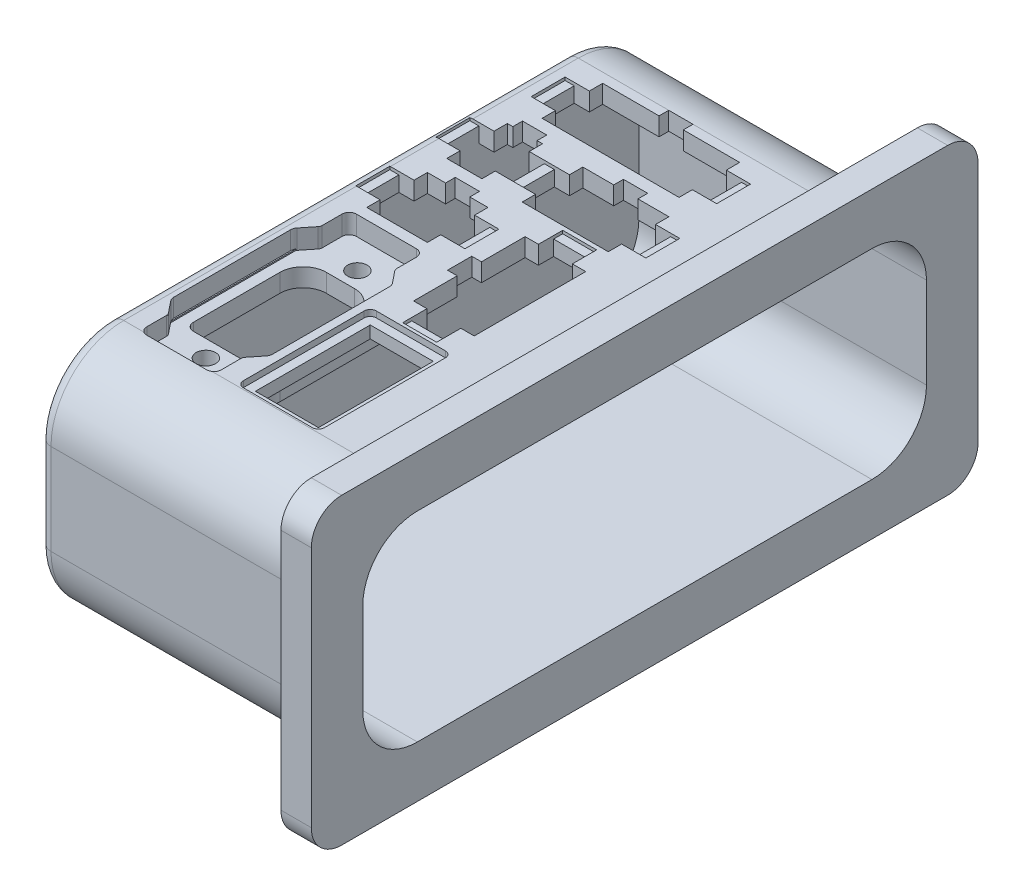
SolidWorks part; units mm, degrees
note: The reader was unsure of these and kept them because the rebuilt part matched: shared geometry of "Sketch1<3>".
ref_plane "Front Plane" through (0, 0, 0) normal (0, 0, 1) x (1, 0, 0)
ref_plane "Top Plane" through (0, 0, 0) normal (0, 1, 0) x (1, 0, 0)
ref_plane "Right Plane" through (0, 0, 0) normal (1, 0, 0) x (0, 0, -1)
sketch "Sketch1" plane through (-330.42, 0, 0) normal (-1, 0, 0) x (0, 0, 1)
  line L47 (-96.595, 23.5) -> (-96.595, 62.5)
  line L48 (-195.595, 23.5) -> (-96.595, 23.5)
  line L49 (-195.595, 62.5) -> (-195.595, 23.5)
  line L50 (-96.595, 62.5) -> (-195.595, 62.5)
  line L51 (-96.595, 35.5) -> (-96.595, 50.5)
  line L52 (-183.595, 23.5) -> (-108.595, 23.5)
  line L53 (-195.595, 50.5) -> (-195.595, 35.5)
  line L54 (-108.595, 62.5) -> (-183.595, 62.5)
  arc A12 (-96.595, 50.5) -> (-108.595, 62.5) centre (-108.595, 50.5) ccw
  arc A13 (-96.595, 35.5) -> (-108.595, 23.5) centre (-108.595, 35.5) cw
  arc A14 (-195.595, 35.5) -> (-183.595, 23.5) centre (-183.595, 35.5) ccw
  arc A15 (-195.595, 50.5) -> (-183.595, 62.5) centre (-183.595, 50.5) cw
  dimension "D1" = 0.5
  dimension "D2" = 12
extrude "Boss-Extrude1" add sketch "Sketch1" against normal blind 10.45
sketch "Sketch2" plane through (-319.97, 0, 0) normal (1, 0, 0) x (0, 0, -1)
  line L10 (51.095, 23) -> (51.095, 63)
  line L11 (46.095, 68) -> (-53.905, 68)
  line L12 (-58.905, 63) -> (-58.905, 23)
  line L13 (-53.905, 18) -> (46.095, 18)
  line L14 (201.095, 18) -> (201.095, 68)
  line L15 (91.095, 18) -> (201.095, 18)
  line L16 (91.095, 68) -> (91.095, 18)
  line L17 (201.095, 68) -> (91.095, 68)
  line L18 (201.095, 23) -> (201.095, 63)
  line L19 (96.095, 18) -> (196.095, 18)
  line L20 (91.095, 63) -> (91.095, 23)
  line L21 (196.095, 68) -> (96.095, 68)
  line L22 (-98.905, 23) -> (-98.905, 63)
  line L23 (-103.905, 68) -> (-203.905, 68)
  line L24 (-208.905, 63) -> (-208.905, 23)
  line L25 (-203.905, 18) -> (-103.905, 18)
  line L27 (-53.905, 63) -> (46.095, 63) construction
  arc A0 (201.095, 63) -> (196.095, 68) centre (196.095, 63) ccw
  arc A1 (201.095, 23) -> (196.095, 18) centre (196.095, 23) cw
  arc A2 (96.095, 18) -> (91.095, 23) centre (96.095, 23) cw
  arc A3 (91.095, 63) -> (96.095, 68) centre (96.095, 63) cw
  arc A4 (51.095, 23) -> (46.095, 18) centre (46.095, 23) cw
  arc A5 (51.095, 63) -> (46.095, 68) centre (46.095, 63) ccw
  arc A6 (-58.905, 63) -> (-53.905, 68) centre (-53.905, 63) cw
  arc A7 (-53.905, 18) -> (-58.905, 23) centre (-53.905, 23) cw
  arc A8 (-98.905, 23) -> (-103.905, 18) centre (-103.905, 23) cw
  arc A9 (-98.905, 63) -> (-103.905, 68) centre (-103.905, 63) ccw
  arc A10 (-208.905, 63) -> (-203.905, 68) centre (-203.905, 63) cw
  arc A11 (-203.905, 18) -> (-208.905, 23) centre (-203.905, 23) cw
  point P44 (-3.905, 63)
  point P45 (-3.905, 68)
  dimension "D2" = 5
  dimension "D1" = 5
  dimension "D3" = 3
extrude "Boss-Extrude2" add sketch "Sketch2" along normal blind 5
delete or keep bodies "Body-Delete/Keep 1" type delete bodies bodies 115
delete or keep bodies "Body-Delete/Keep 2" type delete bodies bodies 114
sketch "Sketch8" plane through (-330.42, 0, 0) normal (-1, 0, 0) x (0, 0, 1)
  line L0 (-108.595, 59.5) -> (-183.595, 59.5)
  line L1 (-192.595, 50.5) -> (-192.595, 35.5)
  line L2 (-183.595, 26.5) -> (-108.595, 26.5)
  line L3 (-99.595, 35.5) -> (-99.595, 50.5)
  line L4 (-108.595, 62.5) -> (-183.595, 62.5)
  line L5 (-195.595, 50.5) -> (-195.595, 35.5)
  line L6 (-183.595, 23.5) -> (-108.595, 23.5)
  line L7 (-96.595, 35.5) -> (-96.595, 50.5)
  line L8 (-108.595, 62.5) -> (-183.595, 62.5)
  line L9 (-195.595, 50.5) -> (-195.595, 35.5)
  line L10 (-183.595, 23.5) -> (-108.595, 23.5)
  line L11 (-96.595, 35.5) -> (-96.595, 50.5)
  line L12 (-195.595, 50.5) -> (-195.595, 62.5)
  line L13 (-195.595, 62.5) -> (-183.595, 62.5)
  line L14 (-183.595, 59.5) -> (-190.595, 59.5)
  line L15 (-192.595, 57.5) -> (-192.595, 50.5)
  line L16 (-108.595, 59.5) -> (-101.595, 59.5)
  line L17 (-99.595, 57.5) -> (-99.595, 50.5)
  line L18 (-96.595, 50.5) -> (-96.595, 62.5)
  line L19 (-96.595, 62.5) -> (-108.595, 62.5)
  arc A2 (-192.595, 35.5) -> (-183.595, 26.5) centre (-183.595, 35.5) ccw
  arc A3 (-108.595, 26.5) -> (-99.595, 35.5) centre (-108.595, 35.5) ccw
  arc A4 (-96.595, 50.5) -> (-108.595, 62.5) centre (-108.595, 50.5) ccw
  arc A5 (-183.595, 62.5) -> (-195.595, 50.5) centre (-183.595, 50.5) ccw
  arc A6 (-195.595, 35.5) -> (-183.595, 23.5) centre (-183.595, 35.5) ccw
  arc A7 (-108.595, 23.5) -> (-96.595, 35.5) centre (-108.595, 35.5) ccw
  arc A10 (-195.595, 35.5) -> (-183.595, 23.5) centre (-183.595, 35.5) ccw
  arc A11 (-108.595, 23.5) -> (-96.595, 35.5) centre (-108.595, 35.5) ccw
  arc A12 (-101.595, 59.5) -> (-99.595, 57.5) centre (-101.595, 57.5) cw
  arc A13 (-190.595, 59.5) -> (-192.595, 57.5) centre (-190.595, 57.5) ccw
  arc A16 (-183.595, 62.5) -> (-195.595, 50.5) centre (-183.595, 50.5) ccw construction
  arc A17 (-183.595, 59.5) -> (-192.595, 50.5) centre (-183.595, 50.5) ccw construction
  arc A18 (-99.595, 50.5) -> (-108.595, 59.5) centre (-108.595, 50.5) ccw construction
  arc A19 (-96.595, 50.5) -> (-108.595, 62.5) centre (-108.595, 50.5) ccw construction
  dimension "D3" = 2
  dimension "D1" = 0
  dimension "D2" = 3
sketch "Sketch10" plane through (-314.97, 0, 0) normal (1, 0, 0) x (0, 0, -1)
  line L4 (183.595, 62.5) -> (108.595, 62.5)
  line L12 (183.595, 62.5) -> (108.595, 62.5)
  line L16 (195.595, 35.5) -> (195.595, 50.5)
  line L18 (195.595, 35.5) -> (195.595, 50.5)
  line L20 (108.595, 23.5) -> (183.595, 23.5)
  line L21 (108.595, 23.5) -> (183.595, 23.5)
  line L22 (96.595, 50.5) -> (96.595, 35.5)
  line L23 (96.595, 50.5) -> (96.595, 35.5)
  arc A4 (108.595, 62.5) -> (96.595, 50.5) centre (108.595, 50.5) ccw
  arc A12 (108.595, 62.5) -> (96.595, 50.5) centre (108.595, 50.5) ccw
  arc A16 (195.595, 50.5) -> (183.595, 62.5) centre (183.595, 50.5) ccw
  arc A18 (195.595, 50.5) -> (183.595, 62.5) centre (183.595, 50.5) ccw
  arc A20 (183.595, 23.5) -> (195.595, 35.5) centre (183.595, 35.5) ccw
  arc A21 (183.595, 23.5) -> (195.595, 35.5) centre (183.595, 35.5) ccw
  arc A22 (96.595, 35.5) -> (108.595, 23.5) centre (108.595, 35.5) ccw
  arc A23 (96.595, 35.5) -> (108.595, 23.5) centre (108.595, 35.5) ccw
  dimension "D1" = 0
extrude "Cut-Extrude1" cut sketch "Sketch10" against normal up to next
extrude "Extrude-Thin1" add sketch "Sketch1<3>" against normal up to surface (15.45 mm away) and the other way blind 35 thin
sketch "Sketch1<3>" plane through (-330.42, 0, 0) normal (-1, 0, 0) x (0, 0, 1) same geometry as "Sketch1"
sketch "Sketch15" plane through (-365.42, 0, 0) normal (-1, 0, 0) x (0, 0, 1)
  line L4 (-108.595, 62.5) -> (-183.595, 62.5)
  line L5 (-195.595, 50.5) -> (-195.595, 35.5)
  line L6 (-183.595, 23.5) -> (-108.595, 23.5)
  line L7 (-96.595, 35.5) -> (-96.595, 50.5)
  line L8 (-108.595, 62.5) -> (-183.595, 62.5)
  line L9 (-195.595, 50.5) -> (-195.595, 35.5)
  line L10 (-183.595, 23.5) -> (-108.595, 23.5)
  line L11 (-96.595, 35.5) -> (-96.595, 50.5)
  arc A4 (-96.595, 50.5) -> (-108.595, 62.5) centre (-108.595, 50.5) ccw
  arc A5 (-183.595, 62.5) -> (-195.595, 50.5) centre (-183.595, 50.5) ccw
  arc A6 (-195.595, 35.5) -> (-183.595, 23.5) centre (-183.595, 35.5) ccw
  arc A7 (-108.595, 23.5) -> (-96.595, 35.5) centre (-108.595, 35.5) ccw
  arc A8 (-96.595, 50.5) -> (-108.595, 62.5) centre (-108.595, 50.5) ccw
  arc A9 (-183.595, 62.5) -> (-195.595, 50.5) centre (-183.595, 50.5) ccw
  arc A10 (-195.595, 35.5) -> (-183.595, 23.5) centre (-183.595, 35.5) ccw
  arc A11 (-108.595, 23.5) -> (-96.595, 35.5) centre (-108.595, 35.5) ccw
  dimension "D1" = 0
extrude "Boss-Extrude4" add sketch "Sketch15" against normal blind 3
fillet "Fillet1" radius 2 8 edges at (-365.42, 27.0147, -192.0803) (-365.42, 43, -195.595) (-365.42, 58.9853, -192.0803) (-365.42, 62.5, -146.095) (-365.42, 58.9853, -100.1097) (-365.42, 43, -96.595) (-365.42, 27.0147, -100.1097) (-365.42, 23.5, -146.095)
sketch "Sketch13" plane through (0, 62.5, 0) normal (0, 1, 0) x (1, 0, 0)
  line L134 (-362.42, 142.795) -> (-346.62, 142.795) construction
  line L135 (-362.42, 142.795) -> (-362.42, 108.595) construction
  line L136 (-362.42, 108.595) -> (-346.62, 108.595) construction
  line L137 (-346.62, 142.795) -> (-346.62, 108.595) construction
  line L230 (-344.495, 181.995) -> (-335.195, 181.995)
  line L231 (-335.195, 174.195) -> (-335.195, 171.995)
  line L232 (-357.795, 181.995) -> (-348.495, 181.995)
  line L233 (-357.795, 181.995) -> (-357.795, 179.795)
  line L234 (-343.895, 144.495) -> (-332.295, 144.495) construction
  line L235 (-357.795, 171.995) -> (-335.195, 171.995)
  line L236 (-335.195, 181.995) -> (-335.195, 179.795)
  line L237 (-359.92, 168.395) -> (-359.02, 168.395)
  line L238 (-359.92, 168.395) -> (-359.92, 166.195)
  line L239 (-359.92, 158.395) -> (-354.12, 158.395)
  line L240 (-357.795, 174.195) -> (-357.795, 171.995)
  line L241 (-354.12, 168.395) -> (-354.12, 166.195)
  line L242 (-342.295, 135.295) -> (-342.295, 142.495)
  line L243 (-342.295, 135.295) -> (-340.095, 135.295)
  line L244 (-332.295, 135.295) -> (-332.295, 153.695)
  line L245 (-363.42, 108.595) -> (-319.97, 108.595) construction
  line L246 (-362.42, 108.595) -> (-362.42, 183.595) construction
  line L247 (-346.62, 108.595) -> (-329.57, 108.595) construction
  line L248 (-344.745, 130.595) -> (-331.445, 130.595) construction
  line L249 (-344.745, 130.595) -> (-344.745, 108.595) construction
  line L250 (-344.745, 108.595) -> (-331.445, 108.595) construction
  line L251 (-342.295, 153.695) -> (-340.095, 153.695)
  line L252 (-359.52, 154.795) -> (-356.52, 154.795)
  line L253 (-359.52, 154.795) -> (-359.52, 152.595)
  line L254 (-359.52, 144.795) -> (-349.52, 144.795)
  line L255 (-349.52, 154.795) -> (-349.52, 152.595)
  line L256 (-347.47, 168.395) -> (-342.37, 168.395)
  line L257 (-347.47, 168.395) -> (-347.47, 166.195)
  line L258 (-347.47, 158.395) -> (-333.27, 158.395)
  line L259 (-333.27, 168.395) -> (-333.27, 166.195)
  line L260 (-348.495, 183.595) -> (-344.495, 183.595)
  line L261 (-348.495, 183.595) -> (-348.495, 181.995)
  line L263 (-344.495, 183.595) -> (-344.495, 181.995)
  line L264 (-360.295, 179.795) -> (-357.795, 179.795)
  line L265 (-360.295, 179.795) -> (-360.295, 174.195)
  line L266 (-360.295, 174.195) -> (-357.795, 174.195)
  line L267 (-332.695, 179.795) -> (-332.695, 174.195)
  line L268 (-362.42, 166.195) -> (-359.92, 166.195)
  line L269 (-362.42, 166.195) -> (-362.42, 160.595)
  line L270 (-362.42, 160.595) -> (-359.92, 160.595)
  line L271 (-351.62, 166.195) -> (-351.62, 160.595)
  line L273 (-359.02, 168.395) -> (-359.02, 169.995)
  line L274 (-359.02, 169.995) -> (-355.02, 169.995)
  line L275 (-355.02, 168.395) -> (-355.02, 169.995)
  line L277 (-342.295, 142.495) -> (-343.895, 142.495)
  line L278 (-343.895, 142.495) -> (-343.895, 146.495)
  line L279 (-342.295, 146.495) -> (-343.895, 146.495)
  line L280 (-340.095, 132.795) -> (-340.095, 135.295)
  line L281 (-340.095, 132.795) -> (-334.495, 132.795)
  line L282 (-334.495, 132.795) -> (-334.495, 135.295)
  line L283 (-340.095, 156.195) -> (-334.495, 156.195)
  line L284 (-349.97, 166.195) -> (-347.47, 166.195)
  line L285 (-349.97, 166.195) -> (-349.97, 160.595)
  line L286 (-349.97, 160.595) -> (-347.47, 160.595)
  line L287 (-330.77, 166.195) -> (-330.77, 160.595)
  line L289 (-342.37, 168.395) -> (-342.37, 169.995)
  line L290 (-342.37, 169.995) -> (-338.37, 169.995)
  line L291 (-338.37, 168.395) -> (-338.37, 169.995)
  line L293 (-356.52, 154.795) -> (-356.52, 156.395)
  line L294 (-356.52, 156.395) -> (-352.52, 156.395)
  line L295 (-352.52, 154.795) -> (-352.52, 156.395)
  line L296 (-362.02, 152.595) -> (-359.52, 152.595)
  line L297 (-362.02, 152.595) -> (-362.02, 146.995)
  line L298 (-362.02, 146.995) -> (-359.52, 146.995)
  line L299 (-347.02, 152.595) -> (-347.02, 146.995)
  line L300 (-335.195, 179.795) -> (-332.695, 179.795)
  line L301 (-335.195, 174.195) -> (-332.695, 174.195)
  line L302 (-355.02, 168.395) -> (-354.12, 168.395)
  line L303 (-354.12, 166.195) -> (-351.62, 166.195)
  line L304 (-354.12, 160.595) -> (-351.62, 160.595)
  line L305 (-354.12, 160.595) -> (-354.12, 158.395)
  line L306 (-352.52, 154.795) -> (-349.52, 154.795)
  line L307 (-349.52, 152.595) -> (-347.02, 152.595)
  line L308 (-349.52, 146.995) -> (-347.02, 146.995)
  line L309 (-359.52, 146.995) -> (-359.52, 144.795)
  line L310 (-349.52, 146.995) -> (-349.52, 144.795)
  line L311 (-338.37, 168.395) -> (-333.27, 168.395)
  line L312 (-333.27, 166.195) -> (-330.77, 166.195)
  line L313 (-333.27, 160.595) -> (-330.77, 160.595)
  line L314 (-347.47, 160.595) -> (-347.47, 158.395)
  line L315 (-333.27, 160.595) -> (-333.27, 158.395)
  line L316 (-342.295, 146.495) -> (-342.295, 153.695)
  line L317 (-340.095, 153.695) -> (-340.095, 156.195)
  line L318 (-334.495, 153.695) -> (-334.495, 156.195)
  line L319 (-334.495, 135.295) -> (-332.295, 135.295)
  line L320 (-334.495, 153.695) -> (-332.295, 153.695)
  line L321 (-359.92, 160.595) -> (-359.92, 158.395)
  line L322 (-331.445, 130.595) -> (-331.445, 108.595) construction
  line L323 (-329.57, 195.595) -> (-329.57, 96.595) construction
  line L324 (-363.42, 195.595) -> (-319.97, 195.595) construction
  line L325 (-363.42, 96.595) -> (-319.97, 96.595) construction
  line L326 (-319.97, 196.095) -> (-319.97, 96.095) construction
  line L327 (-329.57, 183.595) -> (-363.42, 183.595) construction
  line L328 (-363.42, 183.595) -> (-319.97, 183.595) construction
  line L329 (-356.52, 171.995) -> (-356.52, 169.995) construction
  line L330 (-355.02, 158.395) -> (-355.02, 156.395) construction
  line L331 (-356.9837, 144.795) -> (-356.9837, 142.795) construction
  line L333 (-351.62, 164.9343) -> (-349.97, 164.9343) construction
  line L335 (-337.295, 156.195) -> (-337.295, 158.395) construction
  line L336 (-337.295, 132.795) -> (-337.295, 130.595) construction
  point P91 (-338.095, 130.595)
  point P98 (-338.095, 108.595)
  point P100 (-346.495, 183.595)
  point P101 (-346.495, 183.595)
  point P123 (-354.52, 142.795)
  point P124 (-354.52, 144.795)
  point P125 (-338.095, 144.495)
  point P131 (0, 0)
  dimension "D2" = 4
  dimension "D3" = 5.6
  dimension "D4" = 11.6
  dimension "D5" = 10
  dimension "D6" = 27.6
  dimension "D7" = 22.6
  dimension "D8" = 5.6
  dimension "D9" = 10
  dimension "D10" = 11.6
  dimension "D11" = 4
  dimension "D12" = 5.8
  dimension "D13" = 10.8
  dimension "D14" = 4
  dimension "D15" = 34.2
  dimension "D16" = 15.8
  dimension "D17" = 22
  dimension "D18" = 13.3
  dimension "D19" = 5.6
  dimension "D20" = 10
  dimension "D21" = 11.6
  dimension "D22" = 23.4
  dimension "D23" = 18.4
  dimension "D24" = 4
  dimension "D25" = 11.6
  dimension "D26" = 10
  dimension "D27" = 5.6
  dimension "D28" = 15
  dimension "D29" = 10
  dimension "D30" = 4
  dimension "D31" = 11.6
  dimension "D32" = 10
  dimension "D33" = 5.6
  dimension "D34" = 19.2
  dimension "D35" = 14.2
  dimension "D36" = 9.6
  dimension "D37" = 90
  dimension "D38" = 1.2
extrude "Cut-Extrude2" cut sketch "Sketch13" against normal up to next
sketch "Sketch16" plane through (0, 62.5, 0) normal (0, 1, 0) x (1, 0, 0)
  line L24 (-340.095, 135.295) -> (-340.095, 132.795) construction
  line L35 (-356.52, 156.395) -> (-352.52, 156.395) construction
  line L37 (-361.795, 179.795) -> (-331.195, 179.795)
  line L38 (-361.795, 179.795) -> (-361.795, 174.195)
  line L39 (-361.795, 174.195) -> (-331.195, 174.195)
  line L40 (-331.195, 179.795) -> (-331.195, 174.195)
  line L41 (-363.92, 166.195) -> (-329.27, 166.195)
  line L42 (-363.92, 166.195) -> (-363.92, 160.595)
  line L43 (-363.92, 160.595) -> (-329.27, 160.595)
  line L44 (-329.27, 166.195) -> (-329.27, 160.595)
  line L45 (-363.52, 152.595) -> (-345.52, 152.595)
  line L46 (-363.52, 152.595) -> (-363.52, 146.995)
  line L47 (-363.52, 146.995) -> (-345.52, 146.995)
  line L48 (-345.52, 152.595) -> (-345.52, 146.995)
  line L49 (-340.095, 157.695) -> (-334.495, 157.695)
  line L50 (-340.095, 157.695) -> (-340.095, 131.295)
  line L51 (-340.095, 131.295) -> (-334.495, 131.295)
  line L52 (-334.495, 157.695) -> (-334.495, 131.295)
  line L53 (-340.095, 132.795) -> (-334.495, 132.795) construction
  line L54 (-343.895, 146.495) -> (-343.895, 142.495) construction
  line L56 (-362.02, 152.595) -> (-362.02, 146.995) construction
  line L57 (-359.52, 152.595) -> (-362.02, 152.595) construction
  line L58 (-362.42, 166.195) -> (-362.42, 160.595) construction
  line L59 (-359.92, 166.195) -> (-362.42, 166.195) construction
  line L60 (-344.495, 183.595) -> (-348.495, 183.595) construction
  line L61 (-360.295, 179.795) -> (-360.295, 174.195) construction
  line L62 (-357.795, 179.795) -> (-360.295, 179.795) construction
  line L63 (-332.695, 174.195) -> (-332.695, 179.795) construction
  line L64 (-330.77, 160.595) -> (-330.77, 166.195) construction
  line L65 (-347.02, 146.995) -> (-347.02, 152.595) construction
  line L66 (-334.495, 156.195) -> (-340.095, 156.195) construction
  point P22 (-343.895, 144.495)
  point P23 (-340.095, 144.495)
  point P24 (-354.52, 152.595)
  point P35 (-346.495, 183.595)
  point P36 (-346.495, 179.795)
  point P50 (-354.52, 156.395)
  dimension "D1" = 1.5
  dimension "D2" = 1.5
  dimension "D3" = 1.5
  dimension "D4" = 1.5
  dimension "D5" = 1.5
extrude "Cut-Extrude3" cut sketch "Sketch16" against normal blind 0.5
sketch "Sketch21" plane through (0, 62.5, 0) normal (0, 1, 0) x (1, 0, 0)
  line L0 (-360.7953, 138.046) -> (-362.357, 136.0939)
  line L1 (-362.62, 135.3442) -> (-362.62, 116.0458)
  line L2 (-362.357, 115.2961) -> (-360.7953, 113.344)
  line L3 (-360.62, 112.8442) -> (-360.62, 109.595)
  line L4 (-359.42, 108.395) -> (-349.52, 108.395)
  line L5 (-348.32, 109.595) -> (-348.32, 112.8442)
  line L6 (-348.1447, 113.344) -> (-346.583, 115.2961)
  line L7 (-346.32, 116.0458) -> (-346.32, 135.3442)
  line L8 (-346.583, 136.0939) -> (-348.1447, 138.046)
  line L9 (-348.32, 138.5458) -> (-348.32, 141.795)
  line L10 (-349.52, 142.995) -> (-359.42, 142.995)
  line L11 (-360.62, 141.795) -> (-360.62, 138.5458)
  arc A0 (-362.357, 136.0939) -> (-362.62, 135.3442) centre (-361.42, 135.3442) ccw
  arc A1 (-362.62, 116.0458) -> (-362.357, 115.2961) centre (-361.42, 116.0458) ccw
  arc A2 (-360.7953, 113.344) -> (-360.62, 112.8442) centre (-361.42, 112.8442) cw
  arc A3 (-360.62, 109.595) -> (-359.42, 108.395) centre (-359.42, 109.595) ccw
  arc A4 (-349.52, 108.395) -> (-348.32, 109.595) centre (-349.52, 109.595) ccw
  arc A5 (-348.32, 112.8442) -> (-348.1447, 113.344) centre (-347.52, 112.8442) cw
  arc A6 (-346.583, 115.2961) -> (-346.32, 116.0458) centre (-347.52, 116.0458) ccw
  arc A7 (-346.32, 135.3442) -> (-346.583, 136.0939) centre (-347.52, 135.3442) ccw
  arc A8 (-348.1447, 138.046) -> (-348.32, 138.5458) centre (-347.52, 138.5458) cw
  arc A9 (-348.32, 141.795) -> (-349.52, 142.995) centre (-349.52, 141.795) ccw
  arc A10 (-359.42, 142.995) -> (-360.62, 141.795) centre (-359.42, 141.795) ccw
  arc A11 (-360.62, 138.5458) -> (-360.7953, 138.046) centre (-361.42, 138.5458) cw
extrude "Cut-Extrude4" cut sketch "Sketch21" against normal up to surface (3 mm away) up to face at (-350.3061, 59.5, -168.8061)
sketch "Sketch24" plane through (0, 62.5, 0) normal (0, 1, 0) x (1, 0, 0)
  line L0 (-341.595, 109.045) -> (-334.895, 109.045) construction
  line L1 (-343.945, 130.795) -> (-332.545, 130.795)
  line L2 (-344.945, 129.795) -> (-344.945, 109.845)
  line L3 (-343.945, 108.845) -> (-332.545, 108.845)
  line L4 (-331.545, 129.795) -> (-331.545, 109.845)
  line L5 (-331.745, 110.045) -> (-331.745, 129.595) construction
  line L6 (-332.745, 130.595) -> (-334.695, 130.595) construction
  arc A0 (-332.545, 108.845) -> (-331.545, 109.845) centre (-332.545, 109.845) ccw
  arc A1 (-344.945, 109.845) -> (-343.945, 108.845) centre (-343.945, 109.845) ccw
  arc A2 (-343.945, 130.795) -> (-344.945, 129.795) centre (-343.945, 129.795) ccw
  arc A3 (-332.545, 130.795) -> (-331.545, 129.795) centre (-332.545, 129.795) cw
  point P4 (-338.245, 108.845)
  point P7 (-338.245, 109.045)
  point P10 (-331.545, 119.82)
  point P11 (-331.745, 119.82)
  dimension "D3" = 1
  dimension "D1" = 0.2
  dimension "D2" = 0.2
extrude "Cut-Extrude5" cut sketch "Sketch24" against normal blind 1
sketch "Sketch25" plane through (0, 59.5, 0) normal (0, -1, 0) x (1, 0, 0)
  line L0 (-333.045, -110.345) -> (-333.045, -129.295)
  line L1 (-343.245, -110.545) -> (-333.245, -110.545) construction
  line L2 (-343.245, -110.545) -> (-343.245, -129.095) construction
  line L3 (-343.245, -129.095) -> (-333.245, -129.095) construction
  line L4 (-333.245, -110.545) -> (-333.245, -129.095) construction
  line L5 (-343.445, -129.295) -> (-333.045, -129.295)
  line L6 (-343.445, -110.345) -> (-343.445, -129.295)
  line L7 (-343.445, -110.345) -> (-333.045, -110.345)
  dimension "D1" = 0.2
extrude "Cut-Extrude6" cut sketch "Sketch25" against normal through all
sketch "Sketch27" plane through (0, 59.5, 0) normal (0, -1, 0) x (1, 0, 0)
  line L0 (-347.12, -141.795) -> (-347.12, -138.6861)
  line L1 (-347.12, -138.6861) -> (-345.6459, -136.8435)
  line L2 (-345.12, -135.3442) -> (-345.12, -116.0458)
  line L3 (-345.6459, -114.5465) -> (-347.12, -112.7039)
  line L4 (-347.12, -112.7039) -> (-347.12, -109.595)
  line L5 (-349.52, -107.195) -> (-359.42, -107.195)
  line L11 (-359.42, -144.195) -> (-349.52, -144.195)
  line L12 (-348.32, -141.795) -> (-348.32, -138.5458)
  line L13 (-348.1447, -138.046) -> (-346.583, -136.0939)
  line L14 (-346.32, -135.3442) -> (-346.32, -116.0458)
  line L15 (-346.583, -115.2961) -> (-348.1447, -113.344)
  line L16 (-348.32, -112.8442) -> (-348.32, -109.595)
  line L17 (-349.52, -108.395) -> (-359.42, -108.395)
  line L18 (-360.62, -109.595) -> (-360.62, -112.8442)
  line L19 (-360.7953, -113.344) -> (-362.357, -115.2961)
  line L20 (-362.62, -116.0458) -> (-362.62, -135.3442)
  line L21 (-362.357, -136.0939) -> (-360.7953, -138.046)
  line L22 (-360.62, -138.5458) -> (-360.62, -141.795)
  line L23 (-359.42, -142.995) -> (-349.52, -142.995)
  line L24 (-348.32, -141.795) -> (-348.32, -138.5458)
  line L25 (-348.1447, -138.046) -> (-346.583, -136.0939)
  line L26 (-346.32, -135.3442) -> (-346.32, -116.0458)
  line L27 (-346.583, -115.2961) -> (-348.1447, -113.344)
  line L28 (-348.32, -112.8442) -> (-348.32, -109.595)
  line L29 (-349.52, -108.395) -> (-359.42, -108.395)
  line L30 (-360.62, -109.595) -> (-360.62, -112.8442)
  line L31 (-360.7953, -113.344) -> (-362.357, -115.2961)
  line L32 (-362.62, -116.0458) -> (-362.62, -135.3442)
  line L33 (-362.357, -136.0939) -> (-360.7953, -138.046)
  line L34 (-360.62, -138.5458) -> (-360.62, -141.795)
  line L35 (-359.42, -142.995) -> (-349.52, -142.995)
  line L36 (-359.42, -107.195) -> (-363.42, -107.195)
  line L37 (-363.42, -96.595) -> (-363.42, -108.595) construction
  line L38 (-363.42, -107.195) -> (-363.42, -144.195)
  line L39 (-363.42, -108.595) -> (-363.42, -183.595) construction
  line L40 (-363.42, -144.195) -> (-359.42, -144.195)
  line L42 (-361.82, -138.6861) -> (-361.82, -141.795) construction
  line L43 (-363.2941, -136.8435) -> (-361.82, -138.6861) construction
  line L44 (-363.82, -116.0458) -> (-363.82, -135.3442) construction
  line L45 (-361.82, -112.7039) -> (-363.2941, -114.5465) construction
  line L46 (-361.82, -109.595) -> (-361.82, -112.7039) construction
  arc A0 (-347.12, -138.6861) -> (-347.12, -138.6861) centre (-347.12, -138.6861) ccw
  arc A1 (-345.6459, -136.8435) -> (-345.12, -135.3442) centre (-347.52, -135.3442) ccw
  arc A2 (-345.12, -116.0458) -> (-345.6459, -114.5465) centre (-347.52, -116.0458) ccw
  arc A3 (-347.12, -112.7039) -> (-347.12, -112.7039) centre (-347.12, -112.7039) ccw
  arc A4 (-347.12, -109.595) -> (-349.52, -107.195) centre (-349.52, -109.595) ccw
  arc A6 (-361.82, -112.7039) -> (-361.82, -112.7039) centre (-361.82, -112.7039) ccw
  arc A9 (-361.82, -138.6861) -> (-361.82, -138.6861) centre (-361.82, -138.6861) ccw
  arc A11 (-349.52, -144.195) -> (-347.12, -141.795) centre (-349.52, -141.795) ccw
  arc A12 (-348.1447, -138.046) -> (-348.32, -138.5458) centre (-347.52, -138.5458) ccw
  arc A13 (-346.583, -136.0939) -> (-346.32, -135.3442) centre (-347.52, -135.3442) ccw
  arc A14 (-346.32, -116.0458) -> (-346.583, -115.2961) centre (-347.52, -116.0458) ccw
  arc A15 (-348.32, -112.8442) -> (-348.1447, -113.344) centre (-347.52, -112.8442) ccw
  arc A16 (-348.32, -109.595) -> (-349.52, -108.395) centre (-349.52, -109.595) ccw
  arc A17 (-359.42, -108.395) -> (-360.62, -109.595) centre (-359.42, -109.595) ccw
  arc A18 (-360.7953, -113.344) -> (-360.62, -112.8442) centre (-361.42, -112.8442) ccw
  arc A19 (-362.357, -115.2961) -> (-362.62, -116.0458) centre (-361.42, -116.0458) ccw
  arc A20 (-362.62, -135.3442) -> (-362.357, -136.0939) centre (-361.42, -135.3442) ccw
  arc A21 (-360.62, -138.5458) -> (-360.7953, -138.046) centre (-361.42, -138.5458) ccw
  arc A22 (-360.62, -141.795) -> (-359.42, -142.995) centre (-359.42, -141.795) ccw
  arc A23 (-349.52, -142.995) -> (-348.32, -141.795) centre (-349.52, -141.795) ccw
  arc A24 (-348.1447, -138.046) -> (-348.32, -138.5458) centre (-347.52, -138.5458) ccw
  arc A25 (-346.583, -136.0939) -> (-346.32, -135.3442) centre (-347.52, -135.3442) ccw
  arc A26 (-346.32, -116.0458) -> (-346.583, -115.2961) centre (-347.52, -116.0458) ccw
  arc A27 (-348.32, -112.8442) -> (-348.1447, -113.344) centre (-347.52, -112.8442) ccw
  arc A28 (-348.32, -109.595) -> (-349.52, -108.395) centre (-349.52, -109.595) ccw
  arc A29 (-359.42, -108.395) -> (-360.62, -109.595) centre (-359.42, -109.595) ccw
  arc A30 (-360.7953, -113.344) -> (-360.62, -112.8442) centre (-361.42, -112.8442) ccw
  arc A31 (-362.357, -115.2961) -> (-362.62, -116.0458) centre (-361.42, -116.0458) ccw
  arc A32 (-362.62, -135.3442) -> (-362.357, -136.0939) centre (-361.42, -135.3442) ccw
  arc A33 (-360.62, -138.5458) -> (-360.7953, -138.046) centre (-361.42, -138.5458) ccw
  arc A34 (-360.62, -141.795) -> (-359.42, -142.995) centre (-359.42, -141.795) ccw
  arc A35 (-349.52, -142.995) -> (-348.32, -141.795) centre (-349.52, -141.795) ccw
  arc A36 (-361.82, -141.795) -> (-359.42, -144.195) centre (-359.42, -141.795) ccw construction
  arc A37 (-363.82, -135.3442) -> (-363.2941, -136.8435) centre (-361.42, -135.3442) ccw construction
  arc A38 (-363.2941, -114.5465) -> (-363.82, -116.0458) centre (-361.42, -116.0458) ccw construction
  arc A39 (-359.42, -107.195) -> (-361.82, -109.595) centre (-359.42, -109.595) ccw construction
  line M30 (-360.0833, -108.595) -> (-362.42, -108.595)
  line M31 (-362.42, -108.595) -> (-362.42, -115.3825)
  dimension "D1" = 0
  dimension "D2" = 1.2
extrude "Boss-Extrude6" add sketch "Sketch27" along normal blind 0.2 contours L11 A11 L0 L1 A1 L2 A2 L3 L4 A4 L5 L36 L38 L40 A35 L35 A34 L34 A33 L33 A32 L32 A31 A29 L29 A28 L28 A27 L27 A26 L26 A25 L25 A24 L24 M31 M30
sketch "Sketch28" plane through (0, 59.3, 0) normal (0, -1, 0) x (1, 0, 0)
  line L0 (-359.42, -144.195) -> (-349.52, -144.195) construction
  line L1 (-347.12, -141.795) -> (-347.12, -138.6861) construction
  line L2 (-347.12, -138.6861) -> (-345.6459, -136.8435) construction
  line L3 (-345.12, -135.3442) -> (-345.12, -116.0458) construction
  line L4 (-345.6459, -114.5465) -> (-347.12, -112.7039) construction
  line L5 (-347.12, -112.7039) -> (-347.12, -109.595) construction
  line L6 (-349.52, -107.195) -> (-359.42, -107.195) construction
  line L7 (-359.42, -107.195) -> (-363.42, -107.195) construction
  line L8 (-363.42, -107.195) -> (-363.42, -144.195) construction
  line L9 (-363.42, -144.195) -> (-359.42, -144.195) construction
  line L10 (-359.42, -144.195) -> (-349.52, -144.195)
  line L11 (-347.12, -141.795) -> (-347.12, -138.6861)
  line L36 (-347.12, -138.6861) -> (-345.6459, -136.8435)
  line L37 (-345.12, -135.3442) -> (-345.12, -116.0458)
  line L38 (-345.6459, -114.5465) -> (-347.12, -112.7039)
  line L39 (-347.12, -112.7039) -> (-347.12, -109.595)
  line L40 (-349.52, -107.195) -> (-359.42, -107.195)
  line L41 (-359.42, -107.195) -> (-363.42, -107.195)
  line L42 (-363.42, -107.195) -> (-363.42, -144.195)
  line L43 (-363.42, -144.195) -> (-359.42, -144.195)
  line L44 (-359.32, -116.295) -> (-349.62, -116.295) construction
  line L45 (-348.62, -117.295) -> (-348.62, -131.57) construction
  line L46 (-352.145, -135.095) -> (-356.795, -135.095) construction
  line L47 (-360.32, -131.57) -> (-360.32, -117.295) construction
  line L48 (-352.145, -135.395) -> (-356.795, -135.395)
  line L49 (-360.62, -131.57) -> (-360.62, -117.295)
  line L50 (-359.32, -115.995) -> (-349.62, -115.995)
  line L51 (-348.32, -117.295) -> (-348.32, -131.57)
  line L52 (-345.12, -135.3442) -> (-345.12, -116.0458) construction
  arc A0 (-349.52, -144.195) -> (-347.12, -141.795) centre (-349.52, -141.795) ccw construction
  arc A1 (-345.6459, -136.8435) -> (-345.12, -135.3442) centre (-347.52, -135.3442) ccw construction
  arc A2 (-345.12, -116.0458) -> (-345.6459, -114.5465) centre (-347.52, -116.0458) ccw construction
  arc A3 (-347.12, -109.595) -> (-349.52, -107.195) centre (-349.52, -109.595) ccw construction
  arc A4 (-349.52, -144.195) -> (-347.12, -141.795) centre (-349.52, -141.795) ccw
  arc A5 (-345.6459, -136.8435) -> (-345.12, -135.3442) centre (-347.52, -135.3442) ccw
  arc A6 (-345.12, -116.0458) -> (-345.6459, -114.5465) centre (-347.52, -116.0458) ccw
  arc A7 (-347.12, -109.595) -> (-349.52, -107.195) centre (-349.52, -109.595) ccw
  circle A8 centre (-354.47, -138.195) radius 1.6
  circle A9 centre (-354.47, -113.195) radius 1.6
  arc A10 (-349.62, -116.295) -> (-348.62, -117.295) centre (-349.62, -117.295) cw construction
  arc A11 (-348.62, -131.57) -> (-352.145, -135.095) centre (-352.145, -131.57) cw construction
  arc A36 (-356.795, -135.095) -> (-360.32, -131.57) centre (-356.795, -131.57) cw construction
  arc A37 (-360.32, -117.295) -> (-359.32, -116.295) centre (-359.32, -117.295) cw construction
  arc A38 (-348.32, -131.57) -> (-352.145, -135.395) centre (-352.145, -131.57) cw
  arc A39 (-356.795, -135.395) -> (-360.62, -131.57) centre (-356.795, -131.57) cw
  arc A40 (-360.62, -117.295) -> (-359.32, -115.995) centre (-359.32, -117.295) cw
  arc A41 (-349.62, -115.995) -> (-348.32, -117.295) centre (-349.62, -117.295) cw
  point P66 (-354.47, -113.195)
  point P67 (0, 0)
  dimension "D2" = 3.2
  dimension "D3" = 0.3
  dimension "D1" = 1
  dimension "D4" = 3.525
  dimension "D5" = 3.2
  dimension "D6" = 9.35
  dimension "D7" = 15.2
  dimension "D8" = 4.6
  dimension "D9" = 7.4
  dimension "D10" = 26.5
  dimension "D11" = 29.6
extrude "Boss-Extrude7" add sketch "Sketch28" along normal blind 3
